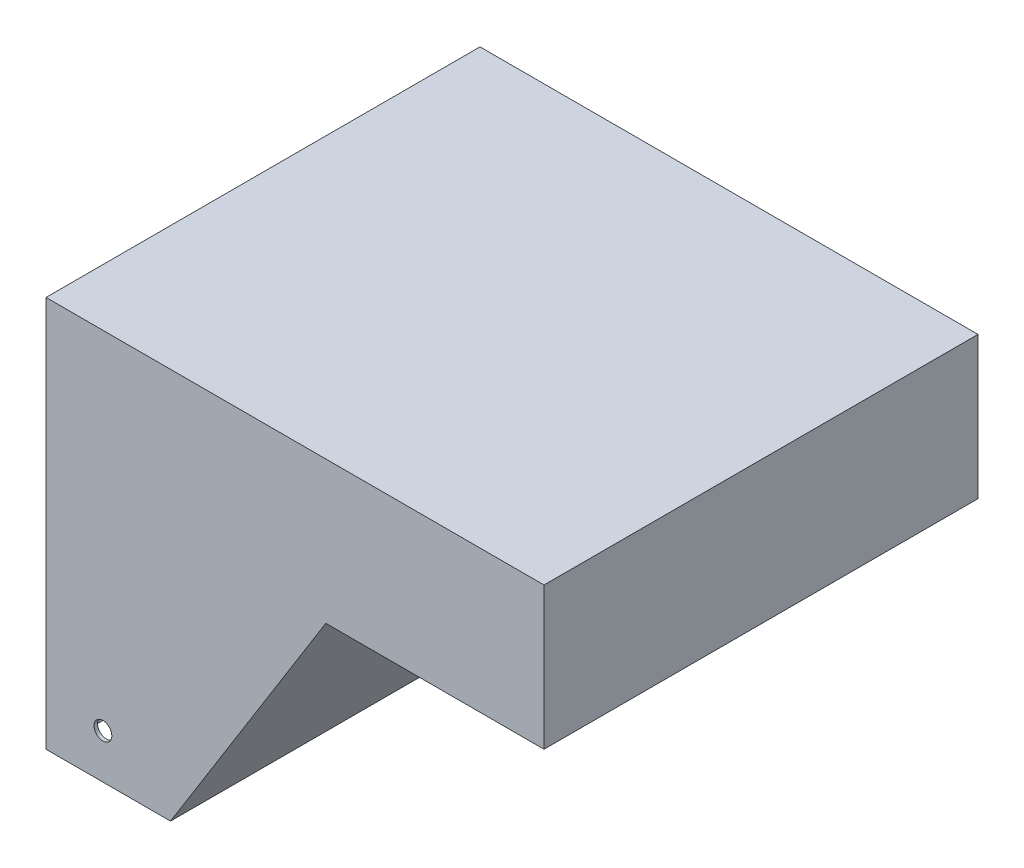
SolidWorks part; units mm, degrees
material "Acrylic (Medium-high impact)"
ref_plane "Front Plane" through (0, 0, 0) normal (0, 0, 1) x (1, 0, 0)
ref_plane "Top Plane" through (0, 0, 0) normal (0, 1, 0) x (1, 0, 0)
ref_plane "Right Plane" through (0, 0, 0) normal (1, 0, 0) x (0, 0, -1)
sketch "Sketch2" plane through (0, 0, 0) normal (0, 0, 1) x (1, 0, 0)
  line L0 (0, 0) -> (355.6, 0)
  line L1 (355.6, 0) -> (355.6, -101.6)
  line L2 (355.6, -101.6) -> (199.8078, -101.6)
  line L3 (199.8078, -101.6) -> (88.9, -279.4)
  line L4 (88.9, -279.4) -> (0, -279.4)
  line L5 (0, -279.4) -> (0, 0)
  circle A0 centre (40.64, -247.65) radius 6.35
  dimension "D6" = 12.7
  dimension "D1" = 355.6
  dimension "D2" = 279.4
  dimension "D3" = 101.6
  dimension "D4" = 88.9
  dimension "D5" = 31.75
  dimension "D7" = 40.64
extrude "Boss-Extrude1" add sketch "Sketch2" along normal blind 2.54
sketch "Sketch3" plane through (0, 0, 2.54) normal (0, 0, 1) x (1, 0, 0)
  line L6 (2.54, -276.86) -> (2.54, -279.4)
  line L7 (0, -279.4) -> (88.9, -279.4) construction
  line L8 (87.4908, -276.86) -> (87.4908, -279.4)
  line L12 (2.54, -2.54) -> (2.54, -276.86)
  line L13 (2.54, -276.86) -> (87.4908, -276.86)
  line L14 (87.4908, -276.86) -> (198.3986, -99.06)
  line L15 (198.3986, -99.06) -> (353.06, -99.06)
  line L16 (353.06, -99.06) -> (353.06, -2.54)
  line L17 (353.06, -2.54) -> (2.54, -2.54)
  line L18 (2.54, -2.54) -> (2.54, -276.86)
  line L20 (87.4908, -276.86) -> (198.3986, -99.06)
  line L21 (198.3986, -99.06) -> (353.06, -99.06)
  line L22 (353.06, -99.06) -> (353.06, -2.54)
  line L23 (353.06, -2.54) -> (2.54, -2.54)
  line M7 (0, 0) -> (0, -279.4)
  line M8 (0, -279.4) -> (88.9, -279.4)
  line M9 (88.9, -279.4) -> (199.8078, -101.6)
  line M10 (199.8078, -101.6) -> (355.6, -101.6)
  line M11 (355.6, -101.6) -> (355.6, 0)
  line M12 (355.6, 0) -> (0, 0)
  dimension "D1" = 2.54
extrude "Boss-Extrude2" add sketch "Sketch3" along normal blind 304.8 contours L23 L22 L21 L20 L18 M12 M7 M8 M9 M10 M11 region at (2.0878, -278.13, 2.54)
ref_plane "Plane1" through (0, 0, 154.94) normal (0, 0, 1) x (1, 0, 0)
mirror "Mirror1" about plane through (0, 0, 154.94) normal (0, 0, 1) of "Boss-Extrude1"
sketch "Sketch4" plane through (0, 0, 0) normal (-1, 0, 0) x (0, 0, 1)
  line L0 (309.88, -279.4) -> (0, -279.4) construction
  line L1 (120.015, -244.851) -> (189.865, -244.851) construction
  circle A0 centre (120.015, -244.851) radius 1.5875
  circle A1 centre (116.84, -273.426) radius 1.5875
  circle A2 centre (189.865, -244.851) radius 1.5875
  circle A3 centre (186.69, -273.426) radius 1.5875
  point P8 (154.94, -279.4)
  point P9 (154.94, -244.851)
  dimension "D1" = 3.175
  dimension "D2" = 69.85
  dimension "D3" = 3.175
  dimension "D4" = 3.175
  dimension "D5" = 28.575
extrude "Cut-Extrude1" cut sketch "Sketch4" against normal up to next
sketch "Sketch5" plane through (0, 0, 0) normal (0, 1, 0) x (1, 0, 0)
  line L0 (355.6, -309.88) -> (355.6, 0) construction
  line L1 (2.54, -2.54) -> (353.06, -2.54)
  line L2 (2.54, -2.54) -> (2.54, -307.34)
  line L3 (2.54, -307.34) -> (353.06, -307.34)
  line L4 (353.06, -2.54) -> (353.06, -307.34)
  line L5 (355.6, -309.88) -> (0, -309.88) construction
  line L6 (355.6, 0) -> (0, 0) construction
  line L7 (0, -309.88) -> (0, 0) construction
  dimension "D1" = 2.54
  dimension "D2" = 2.54
  dimension "D3" = 2.54
  dimension "D4" = 2.54
sketch "Sketch6" plane through (0, 0, 0) normal (-1, 0, 0) x (0, 0, 1)
  line L0 (142.24, -21.6719) -> (167.64, -21.6719) construction
  line L1 (309.88, 0) -> (0, 0) construction
  circle A0 centre (142.24, -21.6719) radius 1.905
  circle A1 centre (167.64, -21.6719) radius 1.905
  point P4 (154.94, 0)
  point P5 (154.94, -21.6719)
  dimension "D2" = 3.81
  dimension "D1" = 25.4
extrude "Cut-Extrude2" cut sketch "Sketch6" against normal up to next
sketch "Sketch7" plane through (0, 0, 0) normal (-1, 0, 0) x (0, 0, 1)
  line L0 (120.015, -109.22) -> (189.865, -109.22) construction
  line L1 (2.54, 0) -> (307.34, 0) construction
  line L2 (309.88, 0) -> (0, 0) construction
  circle A0 centre (120.015, -109.22) radius 2.54
  circle A1 centre (189.865, -109.22) radius 2.54
  circle A2 centre (116.84, -140.97) radius 2.54
  circle A3 centre (186.69, -140.97) radius 2.54
  point P8 (154.94, 0)
  point P9 (154.94, -109.22)
  point P12 (0, 0)
  point P13 (116.84, -140.7212)
  point P14 (120.015, -109.1173)
  dimension "D5" = 5.08
  dimension "D1" = 31.75
  dimension "D2" = 69.85
  dimension "D3" = 3.175
  dimension "D4" = 3.175
  dimension "D6" = 109.22
extrude "Cut-Extrude3" cut sketch "Sketch7" against normal up to next
